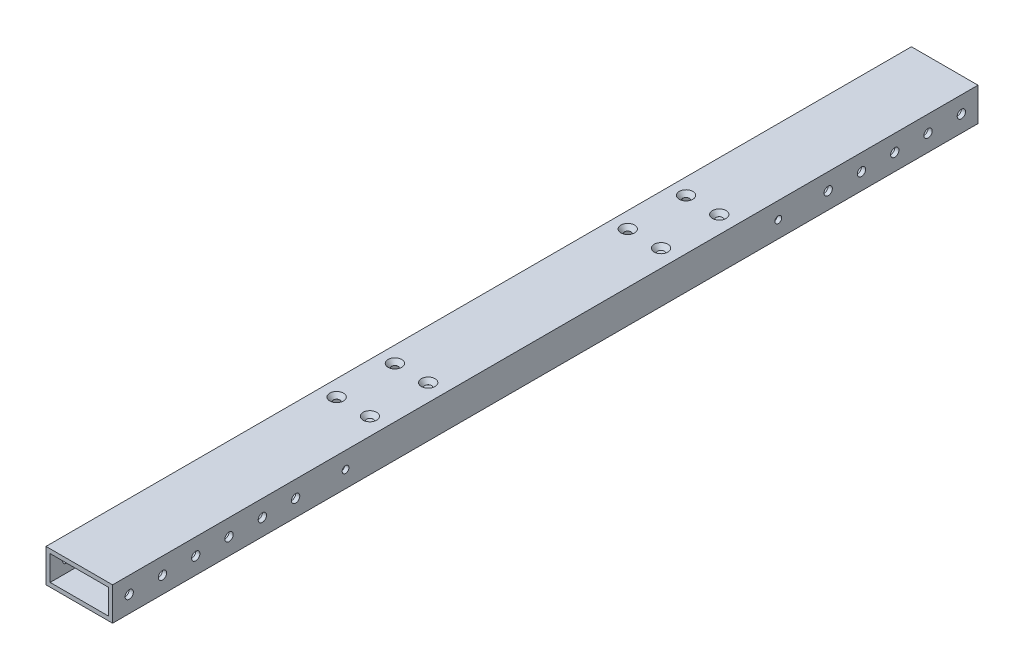
SolidWorks part; units mm, degrees
material "6061 Alloy"
ref_plane "Front Plane" through (0, 0, 0) normal (0, 0, 1) x (1, 0, 0)
ref_plane "Top Plane" through (0, 0, 0) normal (0, 1, 0) x (1, 0, 0)
ref_plane "Right Plane" through (0, 0, 0) normal (1, 0, 0) x (0, 0, -1)
sketch "Sketch1" plane through (0, 0, 0) normal (0, 0, 1) x (1, 0, 0)
  line L0 (-22.225, 9.525) -> (22.225, 9.525)
  line L2 (-25.4, 12.7) -> (25.4, 12.7)
  line L3 (-25.4, 12.7) -> (-25.4, -12.7)
  line L4 (-25.4, -12.7) -> (25.4, -12.7)
  line L5 (25.4, 12.7) -> (25.4, -12.7)
  line L10 (22.225, 9.525) -> (22.225, -9.525)
  line L11 (-22.225, -9.525) -> (22.225, -9.525)
  line L12 (-22.225, 9.525) -> (-22.225, -9.525)
  point P12 (0, 12.7)
  point P14 (25.4, 0)
  dimension "Wall Thickness" = 3.175
  dimension "Outside Width" = 50.8
  dimension "Outside Height" = 25.4
  dimension "Inside Height" = 19.05
  dimension "Inside Width" = 44.45
sketch "Sketch2" plane through (0, 0, 0) normal (1, 0, 0) x (0, 0, -1)
  line L0 (330.2, 0) -> (-330.2, 0)
  point P4 (0, 0)
  point P7 (-330.2, 0)
  point P10 (330.2, 0)
  dimension "Length" = 660.4
sketch "Sketch3" plane through (0, 0, 0) normal (0, 0, 1) x (1, 0, 0)
  line L21 (25.4, 12.7) -> (-25.4, 12.7)
  line L22 (25.4, -12.7) -> (25.4, 12.7)
  line L23 (-25.4, -12.7) -> (25.4, -12.7)
  line L24 (-25.4, 12.7) -> (-25.4, -12.7)
  line L25 (25.4, 12.7) -> (-25.4, 12.7)
  line L26 (25.4, -12.7) -> (25.4, 12.7)
  line L27 (-25.4, -12.7) -> (25.4, -12.7)
  line L28 (-25.4, 12.7) -> (-25.4, -12.7)
  line L29 (22.225, 9.525) -> (-22.225, 9.525)
  line L30 (22.225, -9.525) -> (22.225, 9.525)
  line L31 (-22.225, -9.525) -> (22.225, -9.525)
  line L32 (-22.225, 9.525) -> (-22.225, -9.525)
  line L33 (22.225, 9.525) -> (-22.225, 9.525)
  line L34 (22.225, -9.525) -> (22.225, 9.525)
  line L35 (-22.225, -9.525) -> (22.225, -9.525)
  line L36 (-22.225, 9.525) -> (-22.225, -9.525)
  dimension "D1" = 0
  dimension "D2" = 0
extrude "Boss-Extrude1" add sketch "Sketch3" along normal up to vertex (330.2 mm away) and the other way up to vertex (330.2 mm away) up to point (0, 0, 330.2) other way up to point (0, 0, -330.2)
sketch "Drawing Reference" plane through (0, 0, 0) normal (1, 0, 0) x (0, 0, -1)
  line L0 (-330.2, 0) -> (330.2, 0) construction
  line L1 (0, -12.7) -> (0, 12.7) construction
  line L2 (-330.2, -12.7) -> (330.2, -12.7) construction
  line L5 (-330.2, 12.7) -> (330.2, 12.7) construction
  point P7 (-293.624, 0)
  point P8 (293.624, 0)
  dimension "D1" = 36.576
sketch "Sketch5" plane through (25.4, 0, 0) normal (1, 0, 0) x (0, 0, -1)
  line L2 (-266.7, 0) -> (-241.3, 0)
  line L3 (-241.3, 0) -> (-215.9, 0)
  line L4 (-215.9, 0) -> (-190.5, 0)
  line L5 (-317.5, 0) -> (-330.2, 0)
  line L6 (-330.2, -12.7) -> (-330.2, 12.7) construction
  line L7 (-317.5, 0) -> (-292.1, 0)
  line L8 (-292.1, 0) -> (-266.7, 0)
sketch "Sketch8" plane through (25.4, 0, 0) normal (1, 0, 0) x (0, 0, -1)
  line L0 (330.2, 0) -> (292.1, 0)
  line L1 (330.2, -12.7) -> (330.2, 12.7) construction
  line L2 (292.1, 0) -> (266.7, 0)
  line L3 (266.7, 0) -> (241.3, 0)
  line L4 (241.3, 0) -> (215.9, 0)
  line L5 (330.2, 0) -> (317.5, 0)
hole_wizard "1/4 (0.25) Diameter Hole3" positions "Sketch12" profile "Sketch13" hole size "1/4" standard "ANSI Inch" end condition through all
sketch "Sketch12" plane through (-25.4, 0, 0) normal (-1, 0, 0) x (0, 0, 1)
  point P4 (-317.5, 0)
sketch "Sketch13" plane through (-25.4, 0, -317.5) normal (0, 1, 0) x (0, 0, 1)
  line L0 (0, 0) -> (0, 50.8)
  line L1 (0, 50.8) -> (3.175, 50.8)
  line L2 (3.175, 50.8) -> (3.175, 0)
  line L5 (3.175, 0) -> (0, 0)
  line L11 (0, -6.35) -> (0, 107.95) construction
  dimension "Thru Hole Dia." = 6.35
  dimension "Thru Hole Depth" = 50.8
hole_wizard "1/4 (0.25) Diameter Hole4" positions "Sketch14" profile "Sketch15" hole size "1/4" standard "ANSI Inch" end condition through all
sketch "Sketch14" plane through (-25.4, 0, 0) normal (-1, 0, 0) x (0, 0, 1)
  point P0 (292.1, 0)
  point P3 (317.5, 0)
sketch "Sketch15" plane through (-25.4, 0, 292.1) normal (0, 1, 0) x (0, 0, 1)
  line L0 (0, 0) -> (0, 50.8)
  line L1 (0, 50.8) -> (3.175, 50.8)
  line L2 (3.175, 50.8) -> (3.175, 0)
  line L5 (3.175, 0) -> (0, 0)
  line L11 (0, -6.35) -> (0, 107.95) construction
  dimension "Thru Hole Dia." = 6.35
  dimension "Thru Hole Depth" = 50.8
hole_wizard "1/4 (0.25) Diameter Hole5" positions "Sketch17" profile "Sketch18" hole size "1/4" standard "ANSI Inch" end condition through all
sketch "Sketch17" plane through (25.4, 0, 0) normal (1, 0, 0) x (0, 0, -1)
  point P0 (292.1, 0)
  point P3 (266.7, 0)
sketch "Sketch18" plane through (25.4, 0, -292.1) normal (0, 1, 0) x (0, 0, -1)
  line L0 (0, 0) -> (0, 50.8)
  line L1 (0, 50.8) -> (3.175, 50.8)
  line L2 (3.175, 50.8) -> (3.175, 0)
  line L5 (3.175, 0) -> (0, 0)
  line L11 (0, -6.35) -> (0, 107.95) construction
  dimension "Thru Hole Dia." = 6.35
  dimension "Thru Hole Depth" = 50.8
hole_wizard "1/4 (0.25) Diameter Hole6" positions "Sketch19" profile "Sketch20" hole size "1/4" standard "ANSI Inch" end condition through all
sketch "Sketch19" plane through (25.4, 0, 0) normal (1, 0, 0) x (0, 0, -1)
  point P0 (215.9, 0)
  point P3 (241.3, 0)
sketch "Sketch20" plane through (25.4, 0, -215.9) normal (0, 1, 0) x (0, 0, -1)
  line L0 (0, 0) -> (0, 50.8)
  line L1 (0, 50.8) -> (3.175, 50.8)
  line L2 (3.175, 50.8) -> (3.175, 0)
  line L5 (3.175, 0) -> (0, 0)
  line L11 (0, -6.35) -> (0, 107.95) construction
  dimension "Thru Hole Dia." = 6.35
  dimension "Thru Hole Depth" = 50.8
hole_wizard "1/4 (0.25) Diameter Hole7" positions "Sketch21" profile "Sketch22" hole size "1/4" standard "ANSI Inch" end condition through all
sketch "Sketch21" plane through (25.4, 0, 0) normal (1, 0, 0) x (0, 0, -1)
  point P0 (-190.5, 0)
  point P3 (-215.9, 0)
sketch "Sketch22" plane through (25.4, 0, 190.5) normal (0, 1, 0) x (0, 0, -1)
  line L0 (0, 0) -> (0, 50.8)
  line L1 (0, 50.8) -> (3.175, 50.8)
  line L2 (3.175, 50.8) -> (3.175, 0)
  line L5 (3.175, 0) -> (0, 0)
  line L11 (0, -6.35) -> (0, 107.95) construction
  dimension "Thru Hole Dia." = 6.35
  dimension "Thru Hole Depth" = 50.8
hole_wizard "1/4 (0.25) Diameter Hole8" positions "Sketch23" profile "Sketch24" hole size "1/4" standard "ANSI Inch" end condition through all
sketch "Sketch23" plane through (25.4, 0, 0) normal (1, 0, 0) x (0, 0, -1)
  point P0 (-266.7, 0)
  point P3 (-241.3, 0)
sketch "Sketch24" plane through (25.4, 0, 266.7) normal (0, 1, 0) x (0, 0, -1)
  line L0 (0, 0) -> (0, 50.8)
  line L1 (0, 50.8) -> (3.175, 50.8)
  line L2 (3.175, 50.8) -> (3.175, 0)
  line L5 (3.175, 0) -> (0, 0)
  line L11 (0, -6.35) -> (0, 107.95) construction
  dimension "Thru Hole Dia." = 6.35
  dimension "Thru Hole Depth" = 50.8
sketch "Sketch25" plane through (25.4, 0, 0) normal (1, 0, 0) x (0, 0, -1)
  line L0 (-190.5, 0) -> (-152.4, 0)
  line L1 (215.9, 0) -> (177.8, 0)
hole_wizard "13/64 (0.20313) Diameter Hole1" positions "Sketch26" profile "Sketch27" hole size "13/64" standard "ANSI Inch" end condition through all
sketch "Sketch26" plane through (25.4, 0, 0) normal (1, 0, 0) x (0, 0, -1)
  point P0 (-152.4, 0)
  point P3 (177.8, 0)
sketch "Sketch27" plane through (25.4, 0, 152.4) normal (0, 1, 0) x (0, 0, -1)
  line L0 (0, 0) -> (0, 50.8)
  line L1 (0, 50.8) -> (2.5798, 50.8)
  line L2 (2.5798, 50.8) -> (2.5798, 0)
  line L5 (2.5798, 0) -> (0, 0)
  line L11 (0, -6.35) -> (0, 107.95) construction
  dimension "Thru Hole Dia." = 5.1595
  dimension "Thru Hole Depth" = 50.8
hole_wizard "1/2 (0.5) Diameter Hole1" positions "Sketch33" profile "Sketch34" hole size "1/2" standard "ANSI Inch"
sketch "Sketch33" plane through (-25.4, 0, 0) normal (-1, 0, 0) x (0, 0, 1)
  point P0 (-146.05, 0)
  point P3 (120.65, 0)
sketch "Sketch34" plane through (-25.4, 0, -146.05) normal (0, 1, 0) x (0, 0, 1)
  line L0 (0, 0) -> (0, 10.1655)
  line L1 (0, 10.1655) -> (6.35, 6.35)
  line L2 (6.35, 6.35) -> (6.35, 0)
  line L5 (6.35, 0) -> (0, 0)
  line L10 (0, 10.1655) -> (-6.35, 6.35) construction
  line L11 (0, -6.35) -> (0, 107.95) construction
  dimension "Hole Dia." = 12.7
  dimension "Hole Depth" = 6.35
  dimension "Drill Angle" = 118
sketch "Sketch35" plane through (0, -12.7, 0) normal (0, -1, 0) x (1, 0, 0)
  line L0 (12.192, -101.5498) -> (-13.208, -101.5498) construction
  line L1 (12.192, 120.5998) -> (-13.208, 120.5998) construction
  line L2 (-13.208, 120.5998) -> (-13.208, 76.1498) construction
  line L3 (-13.208, 76.1498) -> (12.192, 76.1498) construction
  line L4 (12.192, 76.1498) -> (12.192, 120.5998) construction
  line L5 (-13.208, -101.5498) -> (-13.208, -145.9998) construction
  line L6 (-13.208, -145.9998) -> (12.192, -145.9998) construction
  line L7 (12.192, -145.9998) -> (12.192, -101.5498) construction
hole_wizard "#10 Clearance Hole1" positions "Sketch39" profile "Sketch40" hole size "#10" standard "ANSI Inch" end condition through all
sketch "Sketch39" plane through (0, -12.7, 0) normal (0, -1, 0) x (-1, 0, 0)
  point P0 (13.208, 145.9998)
  point P3 (-12.192, 145.9998)
  point P6 (-12.192, 101.5498)
  point P9 (13.208, 101.5498)
  point P12 (-12.192, -76.1498)
  point P15 (13.208, -76.1498)
  point P18 (13.208, -120.5998)
  point P21 (-12.192, -120.5998)
sketch "Sketch40" plane through (-13.208, -12.7, -145.9998) normal (1, 0, 0) x (0, 0, -1)
  line L0 (0, 0) -> (0, 25.4)
  line L1 (0, 25.4) -> (5.2197, 25.4)
  line L2 (2.4892, 22.2589) -> (2.4892, 0)
  line L5 (2.4892, 0) -> (0, 0)
  line L7 (5.2197, 25.4) -> (2.4892, 22.2589)
  line L8 (-5.2197, 25.4) -> (-2.4892, 22.2589) construction
  line L11 (0, -6.35) -> (0, 107.95) construction
  dimension "Thru Hole Dia." = 4.9784
  dimension "Thru Hole Depth" = 25.4
  dimension "Far C'Sink Dia." = 10.4394
  dimension "Far C'Sink Angle" = 82
equation "\"D1@Drawing Reference\"=\"Outside Width@Sketch1\" * 0.72"
